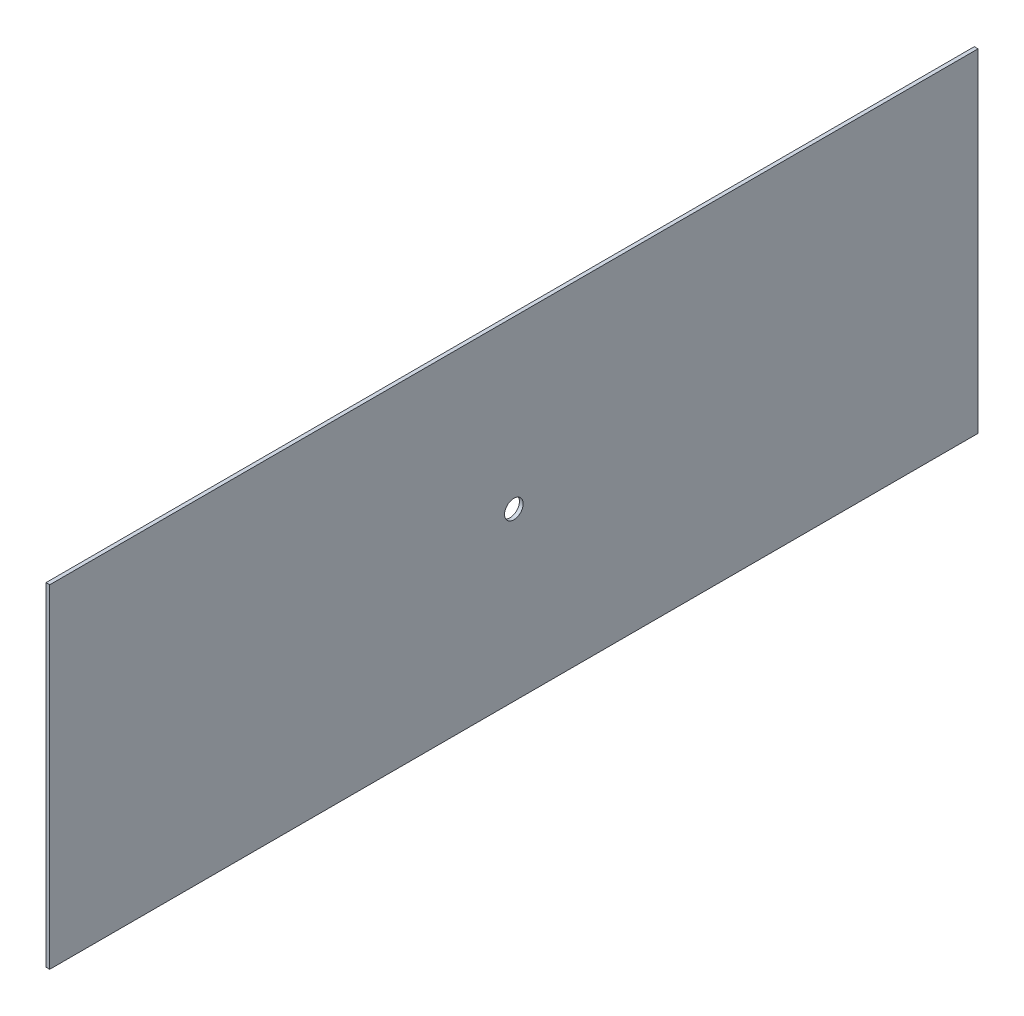
SolidWorks part; units mm, degrees
material "1060 Alloy"
ref_plane "Front Plane" through (0, 0, 0) normal (0, 0, 1) x (1, 0, 0)
ref_plane "Top Plane" through (0, 0, 0) normal (0, 1, 0) x (1, 0, 0)
ref_plane "Right Plane" through (0, 0, 0) normal (1, 0, 0) x (0, 0, -1)
sketch "Sketch1" plane through (0, 0, 0) normal (1, 0, 0) x (0, 0, -1)
  line L1 (-124.7625, -44.7625) -> (124.7625, -44.7625)
  line L2 (-124.7625, -44.7625) -> (-124.7625, 44.7625)
  line L3 (-124.7625, 44.7625) -> (124.7625, 44.7625)
  line L4 (124.7625, -44.7625) -> (124.7625, 44.7625)
  line L5 (-124.7625, -44.7625) -> (124.7625, 44.7625) construction
  line L6 (-124.7625, 44.7625) -> (124.7625, -44.7625) construction
  circle A0 centre (0, 0) radius 2.5
  point P0 (0, 0)
  dimension "D3" = 5
  dimension "D1" = 249.525
  dimension "D2" = 89.525
extrude "Boss-Extrude1" add sketch "Sketch1" along normal blind 1
sketch "Sketch2" [suppressed] plane through (0, 0, 0) normal (0, 1, 0) x (1, 0, 0)
  line L1 (-124.7625, -79.7625) -> (124.7625, -79.7625)
  line L2 (-124.7625, -79.7625) -> (-124.7625, 79.7625)
  line L3 (-124.7625, 79.7625) -> (124.7625, 79.7625)
  line L4 (124.7625, -79.7625) -> (124.7625, 79.7625)
  line L5 (-124.7625, -79.7625) -> (124.7625, 79.7625) construction
  line L6 (-124.7625, 79.7625) -> (124.7625, -79.7625) construction
  circle A0 centre (0, 0) radius 2.5
  point P0 (0, 0)
  dimension "D3" = 5
  dimension "D1" = 249.525
  dimension "D2" = 159.525
extrude "Boss-Extrude2" [suppressed] add sketch "Sketch2" along normal blind 1
